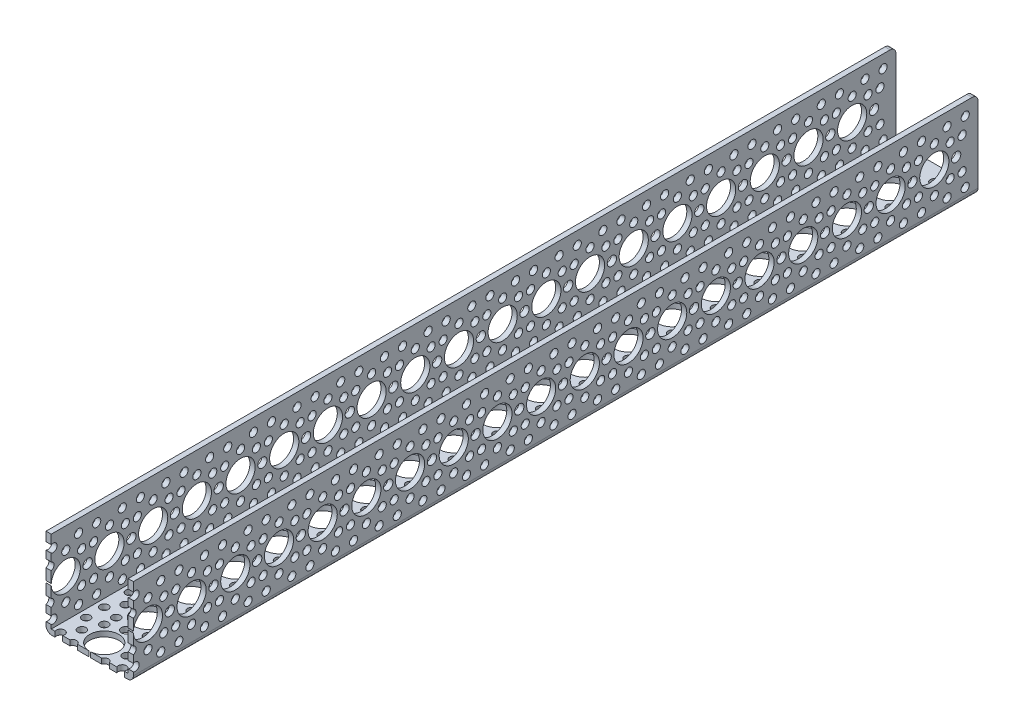
SolidWorks part; units mm, degrees
ref_plane "Front Plane" through (0, 0, 0) normal (0, 0, 1) x (1, 0, 0)
ref_plane "Top Plane" through (0, 0, 0) normal (0, 1, 0) x (1, 0, 0)
ref_plane "Right Plane" through (0, 0, 0) normal (1, 0, 0) x (0, 0, -1)
ref_plane "Plane1" through (38.1, 0, 0) normal (1, 0, 0) x (0, 0, -1)
sketch "Sketch1" plane through (38.1, 0, 0) normal (1, 0, 0) x (0, 0, -1)
  line L0 (0, 38.1) -> (-381, 38.1)
  line L1 (-381, 38.1) -> (-381, 0)
  line L2 (-381, 0) -> (0, 0)
  line L3 (0, 0) -> (0, 38.1)
extrude "Boss-Extrude1" add sketch "Sketch1" against normal blind 38.1
sketch "Sketch2" plane through (0, 0, 381) normal (0, 0, 1) x (1, 0, 0)
  line L0 (35.814, 38.1) -> (2.286, 38.1)
  line L1 (2.286, 38.1) -> (2.286, 2.286)
  line L2 (2.286, 2.286) -> (35.814, 2.286)
  line L3 (35.814, 2.286) -> (35.814, 38.1)
extrude "Cut-Extrude1" cut sketch "Sketch2" against normal through all
hole_wizard "Hole1" positions "Sketch4" profile "Sketch3" legacy
sketch "Sketch4" plane through (0, 0, 0) normal (-1, 0, 0) x (0, 0, 1)
  point P0 (38.1, 19.05)
  point P1 (19.05, 19.05)
  point P2 (57.15, 19.05)
  point P3 (76.2, 19.05)
  point P4 (95.25, 19.05)
  point P5 (114.3, 19.05)
  point P6 (133.35, 19.05)
  point P7 (152.4, 19.05)
  point P8 (171.45, 19.05)
  point P9 (190.5, 19.05)
  point P10 (209.55, 19.05)
  point P11 (228.6, 19.05)
  point P12 (247.65, 19.05)
  point P13 (266.7, 19.05)
  point P14 (285.75, 19.05)
  point P15 (304.8, 19.05)
  point P16 (323.85, 19.05)
  point P17 (342.9, 19.05)
  point P18 (361.95, 19.05)
sketch "Sketch3" plane through (0, 19.05, 38.1) normal (0, 1, 0) x (0, 0, 1)
  line L0 (0, 0) -> (0, 2.286)
  line L1 (0, 2.286) -> (6.3627, 2.286)
  line L2 (6.3627, 2.286) -> (6.3627, 0)
  line L3 (6.3627, 0) -> (0, 0)
  line L4 (0, 110) -> (0, -10) construction
  dimension "Diameter" = 12.7254
  dimension "Depth" = 2.286
hole_wizard "#5 Clearance Hole1" positions "Sketch6" profile "Sketch5" hole size "#5" standard "ANSI Inch"
sketch "Sketch6" plane through (0, 0, 0) normal (-1, 0, 0) x (0, 0, 1)
  point P0 (367.5296, 5.5796)
  point P1 (374.0852, 12.1352)
  point P2 (367.5296, 32.5204)
  point P3 (374.0852, 25.9648)
  point P4 (13.4704, 5.5796)
  point P5 (6.9148, 12.1352)
  point P6 (13.4704, 32.5204)
  point P7 (6.9148, 25.9648)
  point P8 (348.4796, 5.5796)
  point P9 (329.4296, 5.5796)
  point P10 (310.3796, 5.5796)
  point P11 (291.3296, 5.5796)
  point P12 (272.2796, 5.5796)
  point P13 (253.2296, 5.5796)
  point P14 (234.1796, 5.5796)
  point P15 (215.1296, 5.5796)
  point P16 (196.0796, 5.5796)
  point P17 (177.0296, 5.5796)
  point P18 (157.9796, 5.5796)
  point P19 (138.9296, 5.5796)
  point P20 (119.8796, 5.5796)
  point P21 (100.8296, 5.5796)
  point P22 (81.7796, 5.5796)
  point P23 (62.7296, 5.5796)
  point P24 (43.6796, 5.5796)
  point P25 (24.6296, 5.5796)
  point P26 (348.4796, 32.5204)
  point P27 (329.4296, 32.5204)
  point P28 (310.3796, 32.5204)
  point P29 (291.3296, 32.5204)
  point P30 (272.2796, 32.5204)
  point P31 (253.2296, 32.5204)
  point P32 (234.1796, 32.5204)
  point P33 (215.1296, 32.5204)
  point P34 (196.0796, 32.5204)
  point P35 (177.0296, 32.5204)
  point P36 (157.9796, 32.5204)
  point P37 (138.9296, 32.5204)
  point P38 (119.8796, 32.5204)
  point P39 (100.8296, 32.5204)
  point P40 (81.7796, 32.5204)
  point P41 (62.7296, 32.5204)
  point P42 (43.6796, 32.5204)
  point P43 (24.6296, 32.5204)
  point P44 (375.4204, 5.5796)
  point P45 (375.4204, 32.5204)
  point P46 (356.3704, 5.5796)
  point P47 (356.3704, 32.5204)
  point P48 (337.3204, 5.5796)
  point P49 (337.3204, 32.5204)
  point P50 (318.2704, 5.5796)
  point P51 (318.2704, 32.5204)
  point P52 (299.2204, 5.5796)
  point P53 (299.2204, 32.5204)
  point P54 (280.1704, 5.5796)
  point P55 (280.1704, 32.5204)
  point P56 (261.1204, 5.5796)
  point P57 (261.1204, 32.5204)
  point P58 (242.0704, 5.5796)
  point P59 (242.0704, 32.5204)
  point P60 (223.0204, 5.5796)
  point P61 (223.0204, 32.5204)
  point P62 (203.9704, 5.5796)
  point P63 (203.9704, 32.5204)
  point P64 (184.9204, 5.5796)
  point P65 (184.9204, 32.5204)
  point P66 (165.8704, 5.5796)
  point P67 (165.8704, 32.5204)
  point P68 (146.8204, 5.5796)
  point P69 (146.8204, 32.5204)
  point P70 (127.7704, 5.5796)
  point P71 (127.7704, 32.5204)
  point P72 (108.7204, 5.5796)
  point P73 (108.7204, 32.5204)
  point P74 (89.6704, 5.5796)
  point P75 (89.6704, 32.5204)
  point P76 (70.6204, 5.5796)
  point P77 (70.6204, 32.5204)
  point P78 (51.5704, 5.5796)
  point P79 (51.5704, 32.5204)
  point P80 (355.0352, 12.1352)
  point P81 (361.95, 9.271)
  point P82 (368.8648, 12.1352)
  point P83 (368.8648, 25.9648)
  point P84 (361.95, 28.829)
  point P85 (335.9852, 12.1352)
  point P86 (342.9, 9.271)
  point P87 (349.8148, 12.1352)
  point P88 (349.8148, 25.9648)
  point P89 (342.9, 28.829)
  point P90 (316.9352, 12.1352)
  point P91 (323.85, 9.271)
  point P92 (330.7648, 12.1352)
  point P93 (330.7648, 25.9648)
  point P94 (323.85, 28.829)
  point P95 (297.8852, 12.1352)
  point P96 (304.8, 9.271)
  point P97 (311.7148, 12.1352)
  point P98 (311.7148, 25.9648)
  point P99 (304.8, 28.829)
  point P100 (278.8352, 12.1352)
  point P101 (285.75, 9.271)
  point P102 (292.6648, 12.1352)
  point P103 (292.6648, 25.9648)
  point P104 (285.75, 28.829)
  point P105 (259.7852, 12.1352)
  point P106 (266.7, 9.271)
  point P107 (273.6148, 12.1352)
  point P108 (273.6148, 25.9648)
  point P109 (266.7, 28.829)
  point P110 (240.7352, 12.1352)
  point P111 (247.65, 9.271)
  point P112 (254.5648, 12.1352)
  point P113 (254.5648, 25.9648)
  point P114 (247.65, 28.829)
  point P115 (221.6852, 12.1352)
  point P116 (228.6, 9.271)
  point P117 (235.5148, 12.1352)
  point P118 (235.5148, 25.9648)
  point P119 (228.6, 28.829)
  point P120 (202.6352, 12.1352)
  point P121 (209.55, 9.271)
  point P122 (216.4648, 12.1352)
  point P123 (216.4648, 25.9648)
  point P124 (209.55, 28.829)
  point P125 (183.5852, 12.1352)
  point P126 (190.5, 9.271)
  point P127 (197.4148, 12.1352)
  point P128 (197.4148, 25.9648)
  point P129 (190.5, 28.829)
  point P130 (164.5352, 12.1352)
  point P131 (171.45, 9.271)
  point P132 (178.3648, 12.1352)
  point P133 (178.3648, 25.9648)
  point P134 (171.45, 28.829)
  point P135 (145.4852, 12.1352)
  point P136 (152.4, 9.271)
  point P137 (159.3148, 12.1352)
  point P138 (159.3148, 25.9648)
  point P139 (152.4, 28.829)
  point P140 (126.4352, 12.1352)
  point P141 (133.35, 9.271)
  point P142 (140.2648, 12.1352)
  point P143 (140.2648, 25.9648)
  point P144 (133.35, 28.829)
  point P145 (107.3852, 12.1352)
  point P146 (114.3, 9.271)
  point P147 (121.2148, 12.1352)
  point P148 (121.2148, 25.9648)
  point P149 (114.3, 28.829)
  point P150 (88.3352, 12.1352)
  point P151 (95.25, 9.271)
  point P152 (102.1648, 12.1352)
  point P153 (102.1648, 25.9648)
  point P154 (95.25, 28.829)
  point P155 (69.2852, 12.1352)
  point P156 (76.2, 9.271)
  point P157 (83.1148, 12.1352)
  point P158 (83.1148, 25.9648)
  point P159 (76.2, 28.829)
  point P160 (50.2352, 12.1352)
  point P161 (57.15, 9.271)
  point P162 (64.0648, 12.1352)
  point P163 (64.0648, 25.9648)
  point P164 (57.15, 28.829)
  point P165 (31.1852, 12.1352)
  point P166 (38.1, 9.271)
  point P167 (45.0148, 12.1352)
  point P168 (45.0148, 25.9648)
  point P169 (38.1, 28.829)
  point P170 (355.0352, 25.9648)
  point P171 (335.9852, 25.9648)
  point P172 (316.9352, 25.9648)
  point P173 (297.8852, 25.9648)
  point P174 (278.8352, 25.9648)
  point P175 (259.7852, 25.9648)
  point P176 (240.7352, 25.9648)
  point P177 (221.6852, 25.9648)
  point P178 (202.6352, 25.9648)
  point P179 (183.5852, 25.9648)
  point P180 (164.5352, 25.9648)
  point P181 (145.4852, 25.9648)
  point P182 (126.4352, 25.9648)
  point P183 (107.3852, 25.9648)
  point P184 (88.3352, 25.9648)
  point P185 (69.2852, 25.9648)
  point P186 (50.2352, 25.9648)
  point P187 (31.1852, 25.9648)
  point P188 (32.5204, 5.5796)
  point P189 (32.5204, 32.5204)
  point P190 (5.5796, 5.5796)
  point P191 (5.5796, 32.5204)
  point P192 (12.1352, 12.1352)
  point P193 (19.05, 9.271)
  point P194 (25.9648, 12.1352)
  point P195 (25.9648, 25.9648)
  point P196 (19.05, 28.829)
  point P197 (12.1352, 25.9648)
sketch "Sketch5" plane through (0, 5.5796, 367.5296) normal (0, 1, 0) x (0, 0, 1)
  line L0 (0, 0) -> (0, 2.286)
  line L1 (0, 2.286) -> (1.778, 2.286)
  line L2 (1.778, 2.286) -> (1.778, 0)
  line L5 (1.778, 0) -> (0, 0)
  line L11 (0, -6.35) -> (0, 107.95) construction
  dimension "Thru Hole Dia." = 3.556
  dimension "Thru Hole Depth" = 2.286
hole_wizard "#6 Clearance Hole1" positions "Sketch8" profile "Sketch7" hole size "#6" standard "ANSI Inch"
sketch "Sketch8" plane through (0, 0, 0) normal (-1, 0, 0) x (0, 0, 1)
  point P0 (371.475, 19.05)
  point P1 (352.425, 19.05)
  point P2 (333.375, 19.05)
  point P3 (314.325, 19.05)
  point P4 (295.275, 19.05)
  point P5 (276.225, 19.05)
  point P6 (257.175, 19.05)
  point P7 (238.125, 19.05)
  point P8 (219.075, 19.05)
  point P9 (200.025, 19.05)
  point P10 (180.975, 19.05)
  point P11 (161.925, 19.05)
  point P12 (142.875, 19.05)
  point P13 (123.825, 19.05)
  point P14 (104.775, 19.05)
  point P15 (85.725, 19.05)
  point P16 (66.675, 19.05)
  point P17 (47.625, 19.05)
  point P18 (28.575, 19.05)
  point P19 (9.525, 19.05)
sketch "Sketch7" plane through (0, 19.05, 371.475) normal (0, 1, 0) x (0, 0, 1)
  line L0 (0, 0) -> (0, 2.286)
  line L1 (0, 2.286) -> (2.032, 2.286)
  line L2 (2.032, 2.286) -> (2.032, 0)
  line L5 (2.032, 0) -> (0, 0)
  line L11 (0, -6.35) -> (0, 107.95) construction
  dimension "Thru Hole Dia." = 4.064
  dimension "Thru Hole Depth" = 2.286
hole_wizard "Hole2" positions "Sketch10" profile "Sketch9" legacy
sketch "Sketch10" plane through (0, 0, 0) normal (0, -1, 0) x (-1, 0, 0)
  point P0 (-19.05, -361.95)
  point P1 (-19.05, -342.9)
  point P2 (-19.05, -323.85)
  point P3 (-19.05, -304.8)
  point P4 (-19.05, -285.75)
  point P5 (-19.05, -266.7)
  point P6 (-19.05, -247.65)
  point P7 (-19.05, -228.6)
  point P8 (-19.05, -209.55)
  point P9 (-19.05, -190.5)
  point P10 (-19.05, -171.45)
  point P11 (-19.05, -152.4)
  point P12 (-19.05, -133.35)
  point P13 (-19.05, -114.3)
  point P14 (-19.05, -95.25)
  point P15 (-19.05, -76.2)
  point P16 (-19.05, -57.15)
  point P17 (-19.05, -38.1)
  point P18 (-19.05, -19.05)
sketch "Sketch9" plane through (19.05, 0, 361.95) normal (1, 0, 0) x (0, 0, -1)
  line L0 (0, 0) -> (0, 38.1)
  line L1 (0, 38.1) -> (6.3627, 38.1)
  line L2 (6.3627, 38.1) -> (6.3627, 0)
  line L3 (6.3627, 0) -> (0, 0)
  line L4 (0, 110) -> (0, -10) construction
  dimension "Diameter" = 12.7254
  dimension "Depth" = 38.1
hole_wizard "#6 Clearance Hole2" positions "Sketch12" profile "Sketch11" hole size "#6" standard "ANSI Inch"
sketch "Sketch12" plane through (0, 0, 0) normal (0, -1, 0) x (-1, 0, 0)
  point P0 (-19.05, -371.475)
  point P1 (-19.05, -352.425)
  point P2 (-19.05, -333.375)
  point P3 (-19.05, -314.325)
  point P4 (-19.05, -295.275)
  point P5 (-19.05, -276.225)
  point P6 (-19.05, -257.175)
  point P7 (-19.05, -238.125)
  point P8 (-19.05, -219.075)
  point P9 (-19.05, -200.025)
  point P10 (-19.05, -180.975)
  point P11 (-19.05, -161.925)
  point P12 (-19.05, -142.875)
  point P13 (-19.05, -123.825)
  point P14 (-19.05, -104.775)
  point P15 (-19.05, -85.725)
  point P16 (-19.05, -66.675)
  point P17 (-19.05, -47.625)
  point P18 (-19.05, -28.575)
  point P19 (-19.05, -9.525)
sketch "Sketch11" plane through (19.05, 0, 371.475) normal (1, 0, 0) x (0, 0, -1)
  line L0 (0, 0) -> (0, 38.1)
  line L1 (0, 38.1) -> (2.032, 38.1)
  line L2 (2.032, 38.1) -> (2.032, 0)
  line L5 (2.032, 0) -> (0, 0)
  line L11 (0, -6.35) -> (0, 107.95) construction
  dimension "Thru Hole Dia." = 4.064
  dimension "Thru Hole Depth" = 38.1
hole_wizard "#5 Clearance Hole2" positions "Sketch14" profile "Sketch13" hole size "#5" standard "ANSI Inch"
sketch "Sketch14" plane through (0, 0, 0) normal (0, -1, 0) x (-1, 0, 0)
  point P0 (-5.5796, -375.4204)
  point P1 (-5.5796, -367.5296)
  point P2 (-12.1352, -374.0852)
  point P3 (-32.5204, -375.4204)
  point P4 (-32.5204, -367.5296)
  point P5 (-25.9648, -374.0852)
  point P6 (-5.5796, -356.3704)
  point P7 (-5.5796, -348.4796)
  point P8 (-32.5204, -356.3704)
  point P9 (-32.5204, -348.4796)
  point P10 (-5.5796, -337.3204)
  point P11 (-5.5796, -329.4296)
  point P12 (-32.5204, -337.3204)
  point P13 (-32.5204, -329.4296)
  point P14 (-5.5796, -318.2704)
  point P15 (-5.5796, -310.3796)
  point P16 (-32.5204, -318.2704)
  point P17 (-32.5204, -310.3796)
  point P18 (-5.5796, -299.2204)
  point P19 (-5.5796, -291.3296)
  point P20 (-32.5204, -299.2204)
  point P21 (-32.5204, -291.3296)
  point P22 (-5.5796, -280.1704)
  point P23 (-5.5796, -272.2796)
  point P24 (-32.5204, -280.1704)
  point P25 (-32.5204, -272.2796)
  point P26 (-5.5796, -261.1204)
  point P27 (-5.5796, -253.2296)
  point P28 (-32.5204, -261.1204)
  point P29 (-32.5204, -253.2296)
  point P30 (-5.5796, -242.0704)
  point P31 (-5.5796, -234.1796)
  point P32 (-32.5204, -242.0704)
  point P33 (-32.5204, -234.1796)
  point P34 (-5.5796, -223.0204)
  point P35 (-5.5796, -215.1296)
  point P36 (-32.5204, -223.0204)
  point P37 (-32.5204, -215.1296)
  point P38 (-5.5796, -203.9704)
  point P39 (-5.5796, -196.0796)
  point P40 (-32.5204, -203.9704)
  point P41 (-32.5204, -196.0796)
  point P42 (-5.5796, -184.9204)
  point P43 (-5.5796, -177.0296)
  point P44 (-32.5204, -184.9204)
  point P45 (-32.5204, -177.0296)
  point P46 (-5.5796, -165.8704)
  point P47 (-5.5796, -157.9796)
  point P48 (-32.5204, -165.8704)
  point P49 (-32.5204, -157.9796)
  point P50 (-5.5796, -146.8204)
  point P51 (-5.5796, -138.9296)
  point P52 (-32.5204, -146.8204)
  point P53 (-32.5204, -138.9296)
  point P54 (-5.5796, -127.7704)
  point P55 (-5.5796, -119.8796)
  point P56 (-32.5204, -127.7704)
  point P57 (-32.5204, -119.8796)
  point P58 (-5.5796, -108.7204)
  point P59 (-5.5796, -100.8296)
  point P60 (-32.5204, -108.7204)
  point P61 (-32.5204, -100.8296)
  point P62 (-5.5796, -89.6704)
  point P63 (-5.5796, -81.7796)
  point P64 (-32.5204, -89.6704)
  point P65 (-32.5204, -81.7796)
  point P66 (-5.5796, -70.6204)
  point P67 (-5.5796, -62.7296)
  point P68 (-32.5204, -70.6204)
  point P69 (-32.5204, -62.7296)
  point P70 (-5.5796, -51.5704)
  point P71 (-5.5796, -43.6796)
  point P72 (-32.5204, -51.5704)
  point P73 (-32.5204, -43.6796)
  point P74 (-12.1352, -355.0352)
  point P75 (-9.271, -361.95)
  point P76 (-12.1352, -368.8648)
  point P77 (-25.9648, -368.8648)
  point P78 (-28.829, -361.95)
  point P79 (-25.9648, -355.0352)
  point P80 (-12.1352, -335.9852)
  point P81 (-9.271, -342.9)
  point P82 (-12.1352, -349.8148)
  point P83 (-25.9648, -349.8148)
  point P84 (-28.829, -342.9)
  point P85 (-25.9648, -335.9852)
  point P86 (-12.1352, -316.9352)
  point P87 (-9.271, -323.85)
  point P88 (-12.1352, -330.7648)
  point P89 (-25.9648, -330.7648)
  point P90 (-28.829, -323.85)
  point P91 (-25.9648, -316.9352)
  point P92 (-12.1352, -297.8852)
  point P93 (-9.271, -304.8)
  point P94 (-12.1352, -311.7148)
  point P95 (-25.9648, -311.7148)
  point P96 (-28.829, -304.8)
  point P97 (-25.9648, -297.8852)
  point P98 (-12.1352, -278.8352)
  point P99 (-9.271, -285.75)
  point P100 (-12.1352, -292.6648)
  point P101 (-25.9648, -292.6648)
  point P102 (-28.829, -285.75)
  point P103 (-25.9648, -278.8352)
  point P104 (-12.1352, -259.7852)
  point P105 (-9.271, -266.7)
  point P106 (-12.1352, -273.6148)
  point P107 (-25.9648, -273.6148)
  point P108 (-28.829, -266.7)
  point P109 (-25.9648, -259.7852)
  point P110 (-12.1352, -240.7352)
  point P111 (-9.271, -247.65)
  point P112 (-12.1352, -254.5648)
  point P113 (-25.9648, -254.5648)
  point P114 (-28.829, -247.65)
  point P115 (-25.9648, -240.7352)
  point P116 (-12.1352, -221.6852)
  point P117 (-9.271, -228.6)
  point P118 (-12.1352, -235.5148)
  point P119 (-25.9648, -235.5148)
  point P120 (-28.829, -228.6)
  point P121 (-25.9648, -221.6852)
  point P122 (-12.1352, -202.6352)
  point P123 (-9.271, -209.55)
  point P124 (-12.1352, -216.4648)
  point P125 (-25.9648, -216.4648)
  point P126 (-28.829, -209.55)
  point P127 (-25.9648, -202.6352)
  point P128 (-12.1352, -183.5852)
  point P129 (-9.271, -190.5)
  point P130 (-12.1352, -197.4148)
  point P131 (-25.9648, -197.4148)
  point P132 (-28.829, -190.5)
  point P133 (-25.9648, -183.5852)
  point P134 (-12.1352, -164.5352)
  point P135 (-9.271, -171.45)
  point P136 (-12.1352, -178.3648)
  point P137 (-25.9648, -178.3648)
  point P138 (-28.829, -171.45)
  point P139 (-25.9648, -164.5352)
  point P140 (-12.1352, -145.4852)
  point P141 (-9.271, -152.4)
  point P142 (-12.1352, -159.3148)
  point P143 (-25.9648, -159.3148)
  point P144 (-28.829, -152.4)
  point P145 (-25.9648, -145.4852)
  point P146 (-12.1352, -126.4352)
  point P147 (-9.271, -133.35)
  point P148 (-12.1352, -140.2648)
  point P149 (-25.9648, -140.2648)
  point P150 (-28.829, -133.35)
  point P151 (-25.9648, -126.4352)
  point P152 (-12.1352, -107.3852)
  point P153 (-9.271, -114.3)
  point P154 (-12.1352, -121.2148)
  point P155 (-25.9648, -121.2148)
  point P156 (-28.829, -114.3)
  point P157 (-25.9648, -107.3852)
  point P158 (-12.1352, -88.3352)
  point P159 (-9.271, -95.25)
  point P160 (-12.1352, -102.1648)
  point P161 (-25.9648, -102.1648)
  point P162 (-28.829, -95.25)
  point P163 (-25.9648, -88.3352)
  point P164 (-12.1352, -69.2852)
  point P165 (-9.271, -76.2)
  point P166 (-12.1352, -83.1148)
  point P167 (-25.9648, -83.1148)
  point P168 (-28.829, -76.2)
  point P169 (-25.9648, -69.2852)
  point P170 (-12.1352, -50.2352)
  point P171 (-9.271, -57.15)
  point P172 (-12.1352, -64.0648)
  point P173 (-25.9648, -64.0648)
  point P174 (-28.829, -57.15)
  point P175 (-25.9648, -50.2352)
  point P176 (-9.271, -38.1)
  point P177 (-12.1352, -45.0148)
  point P178 (-25.9648, -45.0148)
  point P179 (-28.829, -38.1)
  point P180 (-5.5796, -32.5204)
  point P181 (-5.5796, -24.6296)
  point P182 (-12.1352, -31.1852)
  point P183 (-32.5204, -32.5204)
  point P184 (-32.5204, -24.6296)
  point P185 (-25.9648, -31.1852)
  point P186 (-5.5796, -5.5796)
  point P187 (-5.5796, -13.4704)
  point P188 (-12.1352, -6.9148)
  point P189 (-32.5204, -5.5796)
  point P190 (-32.5204, -13.4704)
  point P191 (-25.9648, -6.9148)
  point P192 (-12.1352, -12.1352)
  point P193 (-9.271, -19.05)
  point P194 (-12.1352, -25.9648)
  point P195 (-25.9648, -25.9648)
  point P196 (-28.829, -19.05)
  point P197 (-25.9648, -12.1352)
sketch "Sketch13" plane through (5.5796, 0, 375.4204) normal (1, 0, 0) x (0, 0, -1)
  line L0 (0, 0) -> (0, 38.1)
  line L1 (0, 38.1) -> (1.778, 38.1)
  line L2 (1.778, 38.1) -> (1.778, 0)
  line L5 (1.778, 0) -> (0, 0)
  line L11 (0, -6.35) -> (0, 107.95) construction
  dimension "Thru Hole Dia." = 3.556
  dimension "Thru Hole Depth" = 38.1
hole_wizard "Hole3" positions "Sketch16" profile "Sketch15" legacy
sketch "Sketch16" plane through (38.1, 0, 0) normal (1, 0, 0) x (0, 0, -1)
  point P0 (-38.1, 19.05)
  point P1 (-19.05, 19.05)
  point P2 (-57.15, 19.05)
  point P3 (-76.2, 19.05)
  point P4 (-95.25, 19.05)
  point P5 (-114.3, 19.05)
  point P6 (-133.35, 19.05)
  point P7 (-152.4, 19.05)
  point P8 (-171.45, 19.05)
  point P9 (-190.5, 19.05)
  point P10 (-209.55, 19.05)
  point P11 (-228.6, 19.05)
  point P12 (-247.65, 19.05)
  point P13 (-266.7, 19.05)
  point P14 (-285.75, 19.05)
  point P15 (-304.8, 19.05)
  point P16 (-323.85, 19.05)
  point P17 (-342.9, 19.05)
  point P18 (-361.95, 19.05)
sketch "Sketch15" plane through (38.1, 19.05, 38.1) normal (0, 1, 0) x (0, 0, -1)
  line L0 (0, 0) -> (0, 38.1)
  line L1 (0, 38.1) -> (6.3627, 38.1)
  line L2 (6.3627, 38.1) -> (6.3627, 0)
  line L3 (6.3627, 0) -> (0, 0)
  line L4 (0, 110) -> (0, -10) construction
  dimension "Diameter" = 12.7254
  dimension "Depth" = 38.1
hole_wizard "#6 Clearance Hole3" positions "Sketch18" profile "Sketch17" hole size "#6" standard "ANSI Inch"
sketch "Sketch18" plane through (38.1, 0, 0) normal (1, 0, 0) x (0, 0, -1)
  point P0 (-352.425, 19.05)
  point P1 (-314.325, 19.05)
  point P2 (-276.225, 19.05)
  point P3 (-238.125, 19.05)
  point P4 (-200.025, 19.05)
  point P5 (-161.925, 19.05)
  point P6 (-123.825, 19.05)
  point P7 (-85.725, 19.05)
  point P8 (-47.625, 19.05)
  point P9 (-28.575, 19.05)
  point P10 (-9.525, 19.05)
  point P11 (-66.675, 19.05)
  point P12 (-104.775, 19.05)
  point P13 (-142.875, 19.05)
  point P14 (-180.975, 19.05)
  point P15 (-219.075, 19.05)
  point P16 (-257.175, 19.05)
  point P17 (-295.275, 19.05)
  point P18 (-333.375, 19.05)
  point P19 (-371.475, 19.05)
sketch "Sketch17" plane through (38.1, 19.05, 352.425) normal (0, 1, 0) x (0, 0, -1)
  line L0 (0, 0) -> (0, 38.1)
  line L1 (0, 38.1) -> (2.032, 38.1)
  line L2 (2.032, 38.1) -> (2.032, 0)
  line L5 (2.032, 0) -> (0, 0)
  line L11 (0, -6.35) -> (0, 107.95) construction
  dimension "Thru Hole Dia." = 4.064
  dimension "Thru Hole Depth" = 38.1
hole_wizard "#5 Clearance Hole3" positions "Sketch20" profile "Sketch19" hole size "#5" standard "ANSI Inch"
sketch "Sketch20" plane through (38.1, 0, 0) normal (1, 0, 0) x (0, 0, -1)
  point P0 (-367.5296, 5.5796)
  point P1 (-367.5296, 32.5204)
  point P2 (-13.4704, 5.5796)
  point P3 (-348.4796, 5.5796)
  point P4 (-310.3796, 5.5796)
  point P5 (-272.2796, 5.5796)
  point P6 (-234.1796, 5.5796)
  point P7 (-196.0796, 5.5796)
  point P8 (-157.9796, 5.5796)
  point P9 (-119.8796, 5.5796)
  point P10 (-81.7796, 5.5796)
  point P11 (-43.6796, 5.5796)
  point P12 (-348.4796, 32.5204)
  point P13 (-310.3796, 32.5204)
  point P14 (-272.2796, 32.5204)
  point P15 (-234.1796, 32.5204)
  point P16 (-196.0796, 32.5204)
  point P17 (-157.9796, 32.5204)
  point P18 (-119.8796, 32.5204)
  point P19 (-81.7796, 32.5204)
  point P20 (-43.6796, 32.5204)
  point P21 (-375.4204, 5.5796)
  point P22 (-356.3704, 5.5796)
  point P23 (-337.3204, 5.5796)
  point P24 (-318.2704, 5.5796)
  point P25 (-299.2204, 5.5796)
  point P26 (-280.1704, 5.5796)
  point P27 (-261.1204, 5.5796)
  point P28 (-242.0704, 5.5796)
  point P29 (-223.0204, 5.5796)
  point P30 (-203.9704, 5.5796)
  point P31 (-184.9204, 5.5796)
  point P32 (-165.8704, 5.5796)
  point P33 (-146.8204, 5.5796)
  point P34 (-127.7704, 5.5796)
  point P35 (-108.7204, 5.5796)
  point P36 (-89.6704, 5.5796)
  point P37 (-70.6204, 5.5796)
  point P38 (-51.5704, 5.5796)
  point P39 (-361.95, 9.271)
  point P40 (-368.8648, 25.9648)
  point P41 (-335.9852, 12.1352)
  point P42 (-349.8148, 12.1352)
  point P43 (-342.9, 28.829)
  point P44 (-323.85, 9.271)
  point P45 (-330.7648, 25.9648)
  point P46 (-297.8852, 12.1352)
  point P47 (-311.7148, 12.1352)
  point P48 (-304.8, 28.829)
  point P49 (-285.75, 9.271)
  point P50 (-292.6648, 25.9648)
  point P51 (-259.7852, 12.1352)
  point P52 (-273.6148, 12.1352)
  point P53 (-266.7, 28.829)
  point P54 (-247.65, 9.271)
  point P55 (-254.5648, 25.9648)
  point P56 (-221.6852, 12.1352)
  point P57 (-235.5148, 12.1352)
  point P58 (-228.6, 28.829)
  point P59 (-209.55, 9.271)
  point P60 (-216.4648, 25.9648)
  point P61 (-183.5852, 12.1352)
  point P62 (-197.4148, 12.1352)
  point P63 (-190.5, 28.829)
  point P64 (-171.45, 9.271)
  point P65 (-178.3648, 25.9648)
  point P66 (-145.4852, 12.1352)
  point P67 (-159.3148, 12.1352)
  point P68 (-152.4, 28.829)
  point P69 (-133.35, 9.271)
  point P70 (-140.2648, 25.9648)
  point P71 (-107.3852, 12.1352)
  point P72 (-121.2148, 12.1352)
  point P73 (-114.3, 28.829)
  point P74 (-95.25, 9.271)
  point P75 (-102.1648, 25.9648)
  point P76 (-69.2852, 12.1352)
  point P77 (-83.1148, 12.1352)
  point P78 (-76.2, 28.829)
  point P79 (-57.15, 9.271)
  point P80 (-64.0648, 25.9648)
  point P81 (-31.1852, 12.1352)
  point P82 (-45.0148, 12.1352)
  point P83 (-38.1, 28.829)
  point P84 (-335.9852, 25.9648)
  point P85 (-297.8852, 25.9648)
  point P86 (-259.7852, 25.9648)
  point P87 (-221.6852, 25.9648)
  point P88 (-183.5852, 25.9648)
  point P89 (-145.4852, 25.9648)
  point P90 (-107.3852, 25.9648)
  point P91 (-69.2852, 25.9648)
  point P92 (-31.1852, 25.9648)
  point P93 (-32.5204, 5.5796)
  point P94 (-32.5204, 32.5204)
  point P95 (-5.5796, 5.5796)
  point P96 (-5.5796, 32.5204)
  point P97 (-12.1352, 12.1352)
  point P98 (-19.05, 9.271)
  point P99 (-25.9648, 12.1352)
  point P100 (-25.9648, 25.9648)
  point P101 (-19.05, 28.829)
  point P102 (-12.1352, 25.9648)
  point P103 (-50.2352, 25.9648)
  point P104 (-88.3352, 25.9648)
  point P105 (-126.4352, 25.9648)
  point P106 (-164.5352, 25.9648)
  point P107 (-202.6352, 25.9648)
  point P108 (-240.7352, 25.9648)
  point P109 (-278.8352, 25.9648)
  point P110 (-316.9352, 25.9648)
  point P111 (-355.0352, 25.9648)
  point P112 (-45.0148, 25.9648)
  point P113 (-38.1, 9.271)
  point P114 (-57.15, 28.829)
  point P115 (-64.0648, 12.1352)
  point P116 (-50.2352, 12.1352)
  point P117 (-83.1148, 25.9648)
  point P118 (-76.2, 9.271)
  point P119 (-95.25, 28.829)
  point P120 (-102.1648, 12.1352)
  point P121 (-88.3352, 12.1352)
  point P122 (-121.2148, 25.9648)
  point P123 (-114.3, 9.271)
  point P124 (-133.35, 28.829)
  point P125 (-140.2648, 12.1352)
  point P126 (-126.4352, 12.1352)
  point P127 (-159.3148, 25.9648)
  point P128 (-152.4, 9.271)
  point P129 (-171.45, 28.829)
  point P130 (-178.3648, 12.1352)
  point P131 (-164.5352, 12.1352)
  point P132 (-197.4148, 25.9648)
  point P133 (-190.5, 9.271)
  point P134 (-209.55, 28.829)
  point P135 (-216.4648, 12.1352)
  point P136 (-202.6352, 12.1352)
  point P137 (-235.5148, 25.9648)
  point P138 (-228.6, 9.271)
  point P139 (-247.65, 28.829)
  point P140 (-254.5648, 12.1352)
  point P141 (-240.7352, 12.1352)
  point P142 (-273.6148, 25.9648)
  point P143 (-266.7, 9.271)
  point P144 (-285.75, 28.829)
  point P145 (-292.6648, 12.1352)
  point P146 (-278.8352, 12.1352)
  point P147 (-311.7148, 25.9648)
  point P148 (-304.8, 9.271)
  point P149 (-323.85, 28.829)
  point P150 (-330.7648, 12.1352)
  point P151 (-316.9352, 12.1352)
  point P152 (-349.8148, 25.9648)
  point P153 (-342.9, 9.271)
  point P154 (-361.95, 28.829)
  point P155 (-368.8648, 12.1352)
  point P156 (-355.0352, 12.1352)
  point P157 (-51.5704, 32.5204)
  point P158 (-70.6204, 32.5204)
  point P159 (-89.6704, 32.5204)
  point P160 (-108.7204, 32.5204)
  point P161 (-127.7704, 32.5204)
  point P162 (-146.8204, 32.5204)
  point P163 (-165.8704, 32.5204)
  point P164 (-184.9204, 32.5204)
  point P165 (-203.9704, 32.5204)
  point P166 (-223.0204, 32.5204)
  point P167 (-242.0704, 32.5204)
  point P168 (-261.1204, 32.5204)
  point P169 (-280.1704, 32.5204)
  point P170 (-299.2204, 32.5204)
  point P171 (-318.2704, 32.5204)
  point P172 (-337.3204, 32.5204)
  point P173 (-356.3704, 32.5204)
  point P174 (-375.4204, 32.5204)
  point P175 (-24.6296, 32.5204)
  point P176 (-62.7296, 32.5204)
  point P177 (-100.8296, 32.5204)
  point P178 (-138.9296, 32.5204)
  point P179 (-177.0296, 32.5204)
  point P180 (-215.1296, 32.5204)
  point P181 (-253.2296, 32.5204)
  point P182 (-291.3296, 32.5204)
  point P183 (-329.4296, 32.5204)
  point P184 (-24.6296, 5.5796)
  point P185 (-62.7296, 5.5796)
  point P186 (-100.8296, 5.5796)
  point P187 (-138.9296, 5.5796)
  point P188 (-177.0296, 5.5796)
  point P189 (-215.1296, 5.5796)
  point P190 (-253.2296, 5.5796)
  point P191 (-291.3296, 5.5796)
  point P192 (-329.4296, 5.5796)
  point P193 (-6.9148, 25.9648)
  point P194 (-13.4704, 32.5204)
  point P195 (-6.9148, 12.1352)
  point P196 (-374.0852, 25.9648)
  point P197 (-374.0852, 12.1352)
sketch "Sketch19" plane through (38.1, 5.5796, 367.5296) normal (0, 1, 0) x (0, 0, -1)
  line L0 (0, 0) -> (0, 38.1)
  line L1 (0, 38.1) -> (1.778, 38.1)
  line L2 (1.778, 38.1) -> (1.778, 0)
  line L5 (1.778, 0) -> (0, 0)
  line L11 (0, -6.35) -> (0, 107.95) construction
  dimension "Thru Hole Dia." = 3.556
  dimension "Thru Hole Depth" = 38.1
fillet "Fillet1" radius 2.54 6 edges at (0, 0, 190.5) (1.143, 38.1, 381) (1.143, 38.1, 0) (36.957, 38.1, 381) (36.957, 38.1, 0) (38.1, 0, 190.5) tangent propagation no
sketch "Sketch21" plane through (38.1, 0, 0) normal (1, 0, 0) x (0, 0, -1)
  line L1 (-381, 58.7299) -> (-368.3, 58.7299)
  line L2 (-381, 58.7299) -> (-381, -41.2206)
  line L3 (-381, -41.2206) -> (-368.3, -41.2206)
  line L4 (-368.3, 58.7299) -> (-368.3, -41.2206)
  dimension "D1" = 12.7
extrude "Cut-Extrude2" cut sketch "Sketch21" against normal blind 76.2
